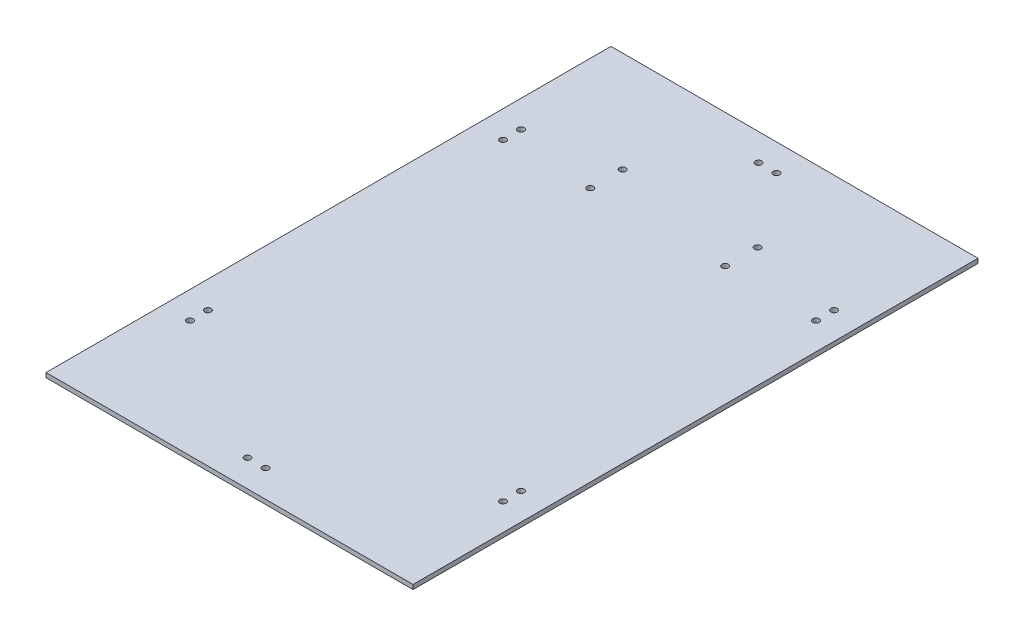
SolidWorks part; units mm, degrees
material "PC High Viscosity"
ref_plane "Front Plane" through (0, 0, 0) normal (0, 0, 1) x (1, 0, 0)
ref_plane "Top Plane" through (0, 0, 0) normal (0, 1, 0) x (1, 0, 0)
ref_plane "Right Plane" through (0, 0, 0) normal (1, 0, 0) x (0, 0, -1)
sketch "Sketch1" plane through (0, 0, 0) normal (0, 1, 0) x (1, 0, 0)
  line L1 (-259.08, 0) -> (0, 0)
  line L2 (-259.08, 0) -> (-259.08, -398.78)
  line L3 (-259.08, -398.78) -> (0, -398.78)
  line L4 (0, 0) -> (0, -398.78)
  point P0 (0, 0)
  point P6 (0, 0)
  dimension "D1" = 259.08
  dimension "D2" = 398.78
extrude "Boss-Extrude1" add sketch "Sketch1" along normal blind 3.175
sketch "Sketch18" plane through (0, 0, 0) normal (0, -1, 0) x (1, 0, 0)
  line L0 (-259.08, 0) -> (-259.08, 398.78) construction
  line L2 (-259.08, 398.78) -> (0, 398.78) construction
  point P0 (-179.705, 93.98)
  point P1 (-84.455, 93.98)
  point P2 (-84.455, 71.12)
  point P3 (-179.705, 71.12)
  dimension "D1" = 22.86
  dimension "D2" = 22.86
  dimension "D3" = 95.25
  dimension "D4" = 95.25
  dimension "D5" = 79.375
  dimension "D6" = 304.8
hole_wizard "#8 Clearance Hole1" positions "Sketch19" profile "Sketch21" hole size "#8" standard "ANSI Inch" end condition through all
sketch "Sketch19" plane through (0, 0, 0) normal (0, -1, 0) x (-1, 0, 0)
  point P0 (84.455, -71.12)
  point P3 (84.455, -93.98)
  point P6 (179.705, -93.98)
  point P9 (179.705, -71.12)
sketch "Sketch21" plane through (-84.455, 0, 71.12) normal (1, 0, 0) x (0, 0, -1)
  line L0 (0, 0) -> (0, 3.175)
  line L1 (0, 3.175) -> (2.2479, 3.175)
  line L2 (2.2479, 3.175) -> (2.2479, 0)
  line L5 (2.2479, 0) -> (0, 0)
  line L11 (0, -6.35) -> (0, 107.95) construction
  dimension "Thru Hole Dia." = 4.4958
  dimension "Thru Hole Depth" = 3.175
sketch "Sketch22" plane through (0, 0, 0) normal (0, -1, 0) x (1, 0, 0)
  line L0 (0, 0) -> (0, 398.78) construction
  line L1 (-259.08, 0) -> (-259.08, 398.78) construction
  line L2 (-259.08, 398.78) -> (0, 398.78) construction
  line L3 (-259.08, 0) -> (0, 0) construction
  point P0 (-19.05, 316.23)
  point P1 (-19.05, 82.55)
  point P2 (-240.03, 82.55)
  point P3 (-240.03, 316.23)
  point P4 (-123.19, 19.05)
  point P5 (-240.03, 303.53)
  point P6 (-19.05, 303.53)
  point P7 (-240.03, 95.25)
  point P16 (-135.89, 19.05)
  point P17 (-135.89, 379.73)
  point P18 (-19.05, 95.25)
  point P19 (-123.19, 379.73)
  dimension "D1" = 19.05
  dimension "D2" = 19.05
  dimension "D3" = 82.55
  dimension "D4" = 82.55
  dimension "D5" = 123.19
  dimension "D6" = 19.05
  dimension "D7" = 123.19
  dimension "D8" = 95.25
  dimension "D9" = 19.05
  dimension "D10" = 19.05
  dimension "D11" = 95.25
  dimension "D12" = 19.05
  dimension "D13" = 19.05
  dimension "D14" = 123.19
  dimension "D15" = 123.19
  dimension "D16" = 19.05
hole_wizard "#8 Clearance Hole2" positions "Sketch23" profile "Sketch24" hole size "#8" standard "ANSI Inch" end condition through all
sketch "Sketch23" plane through (0, 0, 0) normal (0, -1, 0) x (-1, 0, 0)
  point P0 (19.05, -82.55)
  point P3 (135.89, -19.05)
  point P6 (240.03, -82.55)
  point P9 (240.03, -316.23)
  point P12 (123.19, -19.05)
  point P15 (19.05, -316.23)
  point P18 (240.03, -303.53)
  point P21 (240.03, -95.25)
  point P24 (19.05, -95.25)
  point P27 (19.05, -303.53)
  point P31 (123.19, -379.73)
  point P34 (135.89, -379.73)
sketch "Sketch24" plane through (-19.05, 0, 82.55) normal (1, 0, 0) x (0, 0, -1)
  line L0 (0, 0) -> (0, 3.175)
  line L1 (0, 3.175) -> (2.2479, 3.175)
  line L2 (2.2479, 3.175) -> (2.2479, 0)
  line L5 (2.2479, 0) -> (0, 0)
  line L11 (0, -6.35) -> (0, 107.95) construction
  dimension "Thru Hole Dia." = 4.4958
  dimension "Thru Hole Depth" = 3.175
